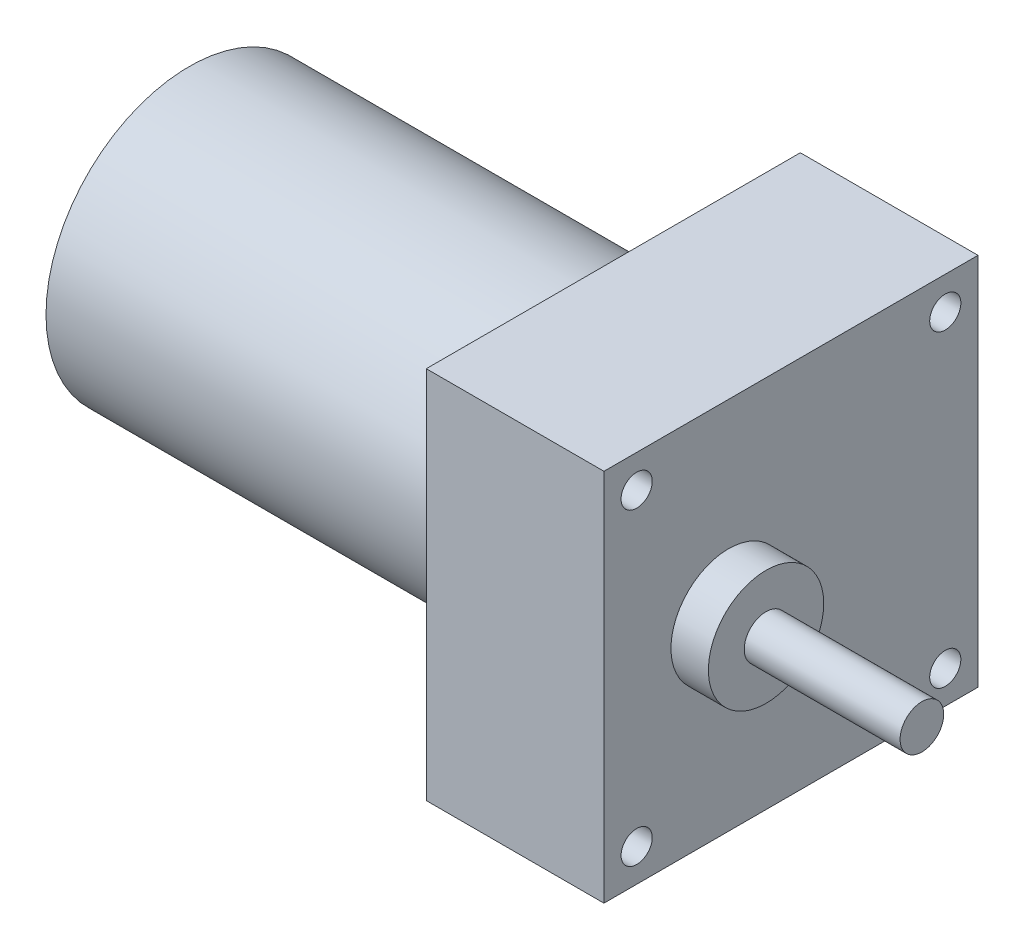
SolidWorks part; units mm, degrees
ref_plane "Front Plane" through (0, 0, 0) normal (1, 0, 0) x (0, 1, 0)
ref_plane "Top Plane" through (0, 0, 0) normal (0, 0, 1) x (0, 1, 0)
ref_plane "Right Plane" through (0, 0, 0) normal (0, 1, 0) x (-1, 0, 0)
sketch "Sketch1" plane through (0, 0, 0) normal (1, 0, 0) x (0, 1, 0)
  line L0 (0, 0) -> (0, -13.4172) construction
  line L1 (-30, -30) -> (30, -30)
  line L2 (-30, -30) -> (-30, 30)
  line L3 (-30, 30) -> (30, 30)
  line L4 (30, -30) -> (30, 30)
  line L5 (-30, -30) -> (30, 30) construction
  line L6 (-30, 30) -> (30, -30) construction
  line L7 (55, 0) -> (-55, 0) construction
  circle A0 centre (-24.75, 24.75) radius 2.5
  circle A1 centre (24.75, 24.75) radius 2.5
  circle A2 centre (24.75, 24.75) radius 2.5
  circle A3 centre (24.75, -24.75) radius 2.5
  circle A4 centre (-24.75, -24.75) radius 2.5
  circle A5 centre (0, 10) radius 3.5
  circle A6 centre (0, 10) radius 9.25
  point P0 (0, 0)
  dimension "D2" = 5
  dimension "D4" = 7
  dimension "D5" = 18.5
  dimension "D1" = 60
  dimension "D3" = 49.5
  dimension "D6" = 10
extrude "Boss-Extrude1" add sketch "Sketch1" along normal blind 28.5 contours L1 L4 L3 L2 A1 A0 A3 A4 | A6 A5 | A5 region at (0, 0, -0.8264) region at (0, 0, 10) region at (0, -8.9884, 10)
extrude "Boss-Extrude2" add sketch "Sketch1<3>" along normal blind 6 from surface contours A6 A5 region at (0, -8.9884, 10) starting at face at (28.5, 24.75, 22.25)
sketch "Sketch1<3>" plane through (0, 0, 0) normal (1, 0, 0) x (0, 1, 0) same geometry as "Sketch1"
extrude "Boss-Extrude3" add sketch "Sketch1<4>" along normal blind 25 from surface separate body contours A5 region at (0, 0, 10) starting at face at (34.5, 0, 0.75)
sketch "Sketch1<4>" plane through (0, 0, 0) normal (1, 0, 0) x (0, 1, 0) same geometry as "Sketch1"
sketch "Sketch2" plane through (0, 0, 0) normal (-1, 0, 0) x (0, -1, 0)
  circle A0 centre (0, 0) radius 23
  dimension "D1" = 46
extrude "Boss-Extrude4" add sketch "Sketch2" along normal blind 68
